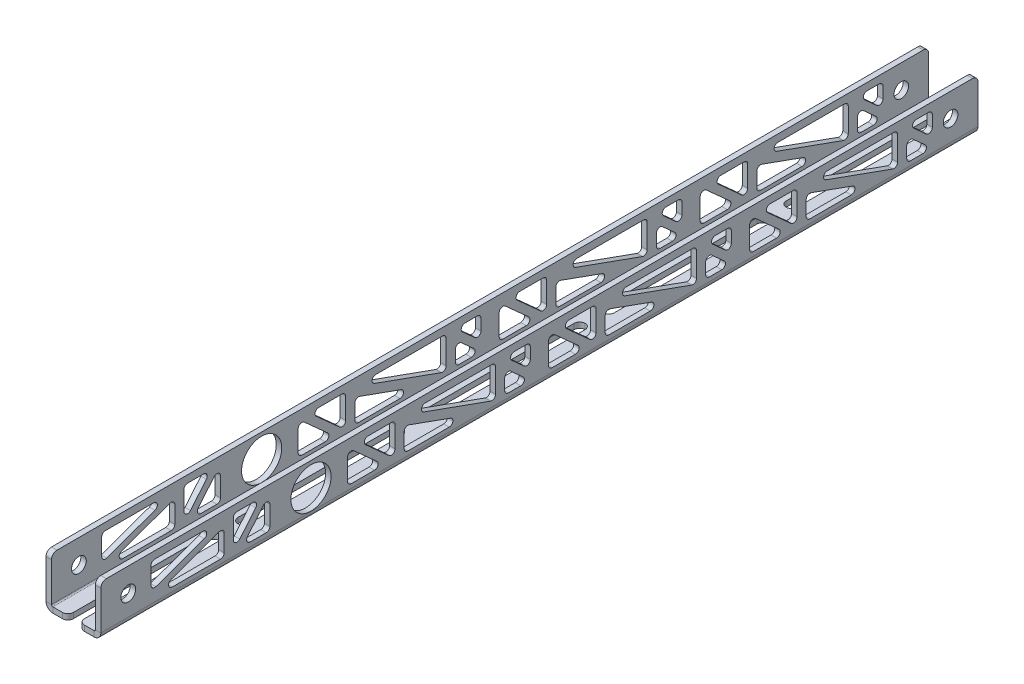
SolidWorks part; units mm, degrees
material "6061 Alloy"
ref_plane "Front Plane" through (0, 0, 0) normal (0, 0, 1) x (1, 0, 0)
ref_plane "Top Plane" through (0, 0, 0) normal (0, 1, 0) x (1, 0, 0)
ref_plane "Right Plane" through (0, 0, 0) normal (1, 0, 0) x (0, 0, -1)
sketch "Sketch1" plane through (0, 0, 0) normal (0, 1, 0) x (1, 0, 0)
  line L1 (-15, -240) -> (15, -240)
  line L2 (-15, -240) -> (-15, 240)
  line L3 (-15, 240) -> (15, 240)
  line L4 (15, -240) -> (15, 240)
  line L5 (0, 240) -> (0, -240) construction
  line L6 (-15, 0) -> (15, 0) construction
  point P0 (0, 0)
  dimension "D1" = 480
  dimension "D2" = 30
base flange "Base-Flange1" sketch "Sketch1" thickness 3 reverse thickness direction no parameters "D1"=0.7366
edge flange "Edge-Flange1" sketch "Sketch10" flange profiles "Sketch10", "Sketch11" flange angle 90 flange length 28 flange position material inside bend radius 0.7366 thickness 3 parameters "D6"=10, "D8"=1
sketch "Sketch10" plane through (-15, 0, 0) normal (-1, 0, 0) x (0, 0, 1)
  line L2 (-240, 0) -> (-240, 25)
  line L3 (-240, 25) -> (240, 25)
  line L4 (240, 25) -> (240, 0)
  line L7 (-240, 0) -> (240, 0) construction
  line L8 (-240, 0) -> (240, 0)
sketch "Sketch11" plane through (15, 0, 0) normal (1, 0, 0) x (0, 0, -1)
  line L2 (240, 0) -> (240, 25)
  line L3 (240, 25) -> (-240, 25)
  line L4 (-240, 25) -> (-240, 0)
  line L13 (-240, 0) -> (240, 0) construction
  line L14 (-240, 0) -> (240, 0)
bend "EdgeBend1" bend radius 0.7366 bend angle 90 parameters "D5"=1
bend "EdgeBend2" bend radius 0.7366 bend angle 90 parameters "D5"=2
sketch "Sketch12" plane through (0, 0, 0) normal (0, 1, 0) x (1, 0, 0)
  line L0 (11.2634, 240) -> (-11.2634, 240) construction
  line L2 (-3, 150) -> (-3, 240)
  line L3 (-3, 240) -> (3, 240)
  line L4 (3, 150) -> (3, 240)
  line L5 (0, 240) -> (0, 150) construction
  line L6 (-3, 195) -> (3, 195) construction
  line L31 (3, 150) -> (-3, 150)
  point P0 (0, 195)
  dimension "D1" = 6
  dimension "D2" = 90
extrude "Cut-Extrude1" cut sketch "Sketch12" against normal through all both and the other way through all normal cut yes
pattern_linear "LPattern1" count 5 spacing 100 along (0, 0, 1) of "Cut-Extrude1"
sketch "Sketch14" plane through (0, 0, 0) normal (1, 0, 0) x (0, 0, -1)
  line L0 (225, 12) -> (-125, 12) construction
  line L1 (240, 0.7366) -> (240, 25) construction
  circle A7 centre (-125, 12) radius 11
  circle A20 centre (225, 12) radius 15 construction
  circle A21 centre (225, 12) radius 4
  circle A22 centre (-225, 12) radius 4.05
  point P6 (50, 12)
  dimension "D1" = 30
  dimension "D3" = 22
  dimension "D6" = 8
  dimension "D11" = 8.1
  dimension "D2" = 350
  dimension "D7" = 15
  dimension "D10" = 12
  dimension "D12" = 100
extrude "Cut-Extrude2" cut sketch "Sketch14" against normal through all both and the other way through all normal cut yes
fillet "Fillet1" radius 3 24 edges at (-13.5, 25, 240) (-3, -1.5, 60) (3, -1.5, 60) (13.5, 25, 240) (13.5, 25, -240) (3, -1.5, -240) (3, -1.5, -150) (-3, -1.5, -150) (-3, -1.5, -240) (-13.5, 25, -240) (3, -1.5, 50) (-3, -1.5, 50) (-3, -1.5, -40) (3, -1.5, -50) (-3, -1.5, -50) (3, -1.5, -40) (3, -1.5, -140) (-3, -1.5, -140) (-3, -1.5, 160) (-3, -1.5, 240) (3, -1.5, 240) (3, -1.5, 160) (3, -1.5, 150) (-3, -1.5, 150)
sketch "Sketch15" plane through (0, 0, 0) normal (1, 0, 0) x (0, 0, -1)
  line L0 (-225, 12) -> (225, 12) construction
  line L1 (-105, 21) -> (-105, 3)
  line L2 (-105, 3) -> (-5, 3) construction
  line L3 (-105, 3) -> (-105, 21) construction
  line L4 (-105, 21) -> (-5, 21) construction
  line L5 (-5, 3) -> (-5, 21) construction
  line L6 (-55, 21) -> (-55, 3) construction
  line L7 (-105, 12) -> (-5, 12) construction
  line L8 (-105, 3) -> (-85, 3)
  line L9 (-85, 3) -> (-105, 21)
  line L10 (-99, 21) -> (-79, 3)
  line L11 (-79, 3) -> (-79, 21)
  line L12 (-79, 21) -> (-99, 21)
  line L13 (-74, 21) -> (-24, 3)
  line L14 (-24, 3) -> (-24, 21)
  line L15 (-24, 21) -> (-74, 21)
  line L16 (-74, 3) -> (-74, 16)
  line L17 (-74, 16) -> (-37.8889, 3)
  line L18 (-37.8889, 3) -> (-74, 3)
  line L19 (-19, 21) -> (-5, 8.3844)
  line L20 (-5, 8.3844) -> (-5, 21)
  line L21 (-5, 21) -> (-19, 21)
  line L22 (-19, 3) -> (-5, 3)
  line L23 (-5, 3) -> (-19, 15.6156)
  line L24 (-19, 15.6156) -> (-19, 3)
  line L25 (-125, 1) -> (-125, 23) construction
  circle A0 centre (-125, 12) radius 11 construction
  point P4 (-55, 12)
  point P33 (-125, 12)
  dimension "D1" = 55
  dimension "D2" = 100
  dimension "D3" = 18
  dimension "D4" = 6
  dimension "D5" = 20
  dimension "D6" = 5
  dimension "D7" = 5
  dimension "D8" = 50
  dimension "D9" = 5
  dimension "D10" = 4
extrude "Cut-Extrude3" cut sketch "Sketch15" against normal through all both and the other way through all normal cut yes
pattern_linear "LPattern2" count 3 spacing 110 along (0, 0, -1) of "Cut-Extrude3"
sketch "Sketch16" plane through (0, 0, 0) normal (1, 0, 0) x (0, 0, -1)
  line L1 (-147.5, 3) -> (-147.5, 21) construction
  line L2 (-212.5, 3) -> (-172.5, 3)
  line L3 (-172.5, 17.2835) -> (-212.5, 3)
  line L4 (-172.5, 3) -> (-172.5, 17.2835)
  line L5 (-212.5, 21) -> (-172.5, 21)
  line L6 (-167.5, 21) -> (-152.5, 21)
  line L7 (-167.5, 3) -> (-167.5, 21)
  line L8 (-152.5, 21) -> (-167.5, 3)
  line L9 (-162.5, 3) -> (-147.5, 21)
  line L10 (-147.5, 3) -> (-162.5, 3)
  line L11 (-147.5, 21) -> (-147.5, 3) construction
  line L12 (-212.5, 21) -> (-212.5, 6.7165)
  line L13 (-212.5, 6.7165) -> (-172.5, 21)
  line L14 (-225, 12) -> (-125, 12) construction
  line L16 (-212.5, 21) -> (-147.5, 21) construction
  line L17 (-212.5, 21) -> (-212.5, 3) construction
  line L18 (-212.5, 3) -> (-147.5, 3) construction
  line L19 (-147.5, 21) -> (-147.5, 3)
  line L20 (-212.5, 21) -> (-147.5, 3) construction
  line L21 (-212.5, 3) -> (-147.5, 21) construction
  point P20 (-180, 12)
  dimension "D1" = 5
  dimension "D2" = 5
  dimension "D3" = 3.5
  dimension "D4" = 65
  dimension "D5" = 45
  dimension "D6" = 18
  dimension "D7" = 40
extrude "Cut-Extrude4" cut sketch "Sketch16" against normal through all both and the other way through all normal cut yes
fillet "Fillet2" radius 2 132 edges at (13.5, 8.3844, 5) (13.5, 21, 19) (13.5, 21, 5) (13.5, 3, 79) (13.5, 21, 99) (13.5, 21, 79) (13.5, 21, 105) (13.5, 3, 85) (13.5, 3, 105) (13.5, 16, 74) (13.5, 3, 37.8889) (13.5, 3, 74) (13.5, 3, 24) (13.5, 21, 74) (13.5, 21, 24) (13.5, 3, 5) (13.5, 3, 19) (13.5, 15.6156, 19) (13.5, 21, -105) (13.5, 8.3844, -105) (13.5, 21, -91) (13.5, 21, -215) (13.5, 8.3844, -215) (13.5, 21, -201) (13.5, 21, -31) (13.5, 3, -31) (13.5, 21, -11) (13.5, 21, -141) (13.5, 3, -141) (13.5, 21, -121) (13.5, 3, -5) (13.5, 21, -5) (13.5, 3, -25) (13.5, 3, -115) (13.5, 21, -115) (13.5, 3, -135) (13.5, 3, -36) (13.5, 16, -36) (13.5, 3, -72.1111) (13.5, 3, -146) (13.5, 16, -146) (13.5, 3, -182.1111) (13.5, 21, -86) (13.5, 3, -86) (13.5, 21, -36) (13.5, 21, -196) (13.5, 3, -196) (13.5, 21, -146) (13.5, 15.6156, -91) (13.5, 3, -105) (13.5, 3, -91) (13.5, 15.6156, -201) (13.5, 3, -215) (13.5, 3, -201) (13.5, 3, 162.5) (13.5, 21, 147.5) (13.5, 3, 172.5) (13.5, 3, 212.5) (13.5, 17.2835, 172.5) (13.5, 21, 212.5) (13.5, 21, 172.5) (13.5, 6.7165, 212.5) (13.5, 21, 152.5) (13.5, 3, 167.5) (13.5, 21, 167.5) (13.5, 3, 147.5) (-13.5, 8.3844, 5) (-13.5, 21, 19) (-13.5, 21, 5) (-13.5, 3, 79) (-13.5, 21, 99) (-13.5, 21, 79) (-13.5, 21, 105) (-13.5, 3, 85) (-13.5, 3, 105) (-13.5, 16, 74) (-13.5, 3, 37.8889) (-13.5, 3, 74) (-13.5, 3, 24) (-13.5, 21, 74) (-13.5, 21, 24) (-13.5, 3, 5) (-13.5, 3, 19) (-13.5, 15.6156, 19) (-13.5, 3, -105) (-13.5, 3, -91) (-13.5, 15.6156, -91) (-13.5, 3, -215) (-13.5, 3, -201) (-13.5, 15.6156, -201) (-13.5, 8.3844, -105) (-13.5, 21, -91) (-13.5, 21, -105) (-13.5, 8.3844, -215) (-13.5, 21, -201) (-13.5, 21, -215) (-13.5, 3, -31) (-13.5, 21, -11) (-13.5, 21, -31) (-13.5, 3, -141) (-13.5, 21, -121) (-13.5, 21, -141) (-13.5, 21, -5) (-13.5, 3, -25) (-13.5, 3, -5) (-13.5, 21, -115) (-13.5, 3, -135) (-13.5, 3, -115) (-13.5, 16, -36) (-13.5, 3, -72.1111) (-13.5, 3, -36) (-13.5, 16, -146) (-13.5, 3, -182.1111) (-13.5, 3, -146) (-13.5, 3, -86) (-13.5, 21, -36) (-13.5, 21, -86) (-13.5, 3, -196) (-13.5, 21, -146) (-13.5, 21, -196) (-13.5, 3, 162.5) (-13.5, 21, 147.5) (-13.5, 3, 147.5) (-13.5, 3, 212.5) (-13.5, 17.2835, 172.5) (-13.5, 21, 212.5) (-13.5, 21, 172.5) (-13.5, 6.7165, 212.5) (-13.5, 21, 152.5) (-13.5, 3, 167.5) (-13.5, 21, 167.5) (-13.5, 3, 172.5)
sketch "Bend-Lines1" plane through (0, 0, 0) normal (0, 1, 0) x (1, 0, 0)
sketch "Bounding-Box1" plane through (0, 0, 0) normal (0, 1, 0) x (1, 0, 0)
